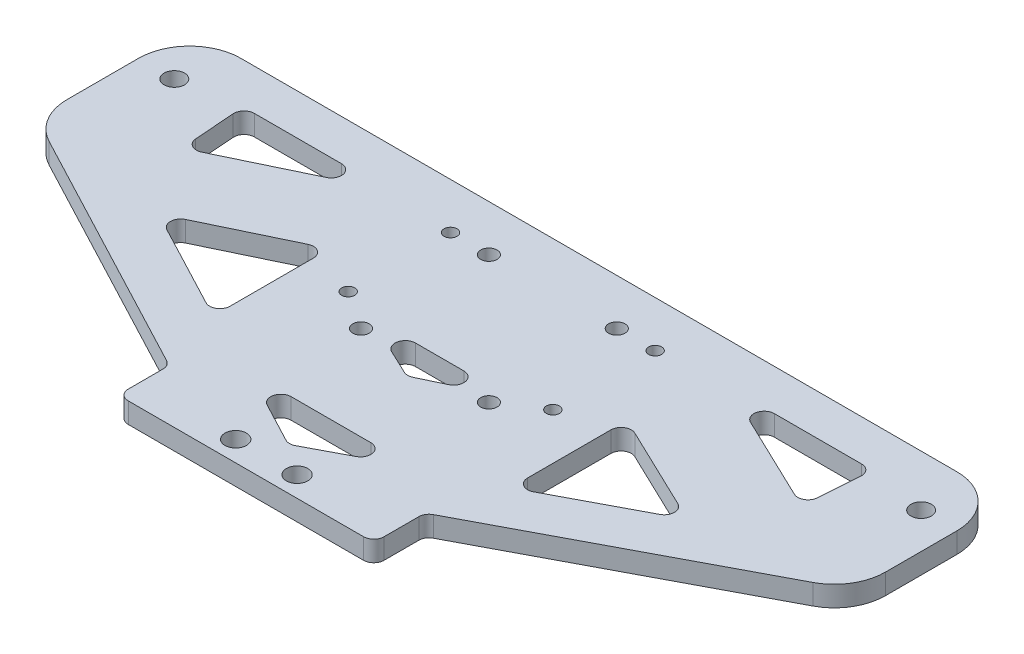
SolidWorks part; units mm, degrees
material "Thornel Mat VMA"
ref_plane "Front" through (0, 0, 0) normal (0, 0, 1) x (1, 0, 0)
ref_plane "Top" through (0, 0, 0) normal (0, 1, 0) x (1, 0, 0)
ref_plane "Right" through (0, 0, 0) normal (1, 0, 0) x (0, 0, -1)
sketch "草图1" plane through (0, 0, 0) normal (0, 1, 0) x (1, 0, 0)
  line L0 (0, 40.0348) -> (0, 0) construction
  line L1 (25, 0) -> (-25, 0)
  line L2 (-25, 0) -> (-80, 29)
  line L3 (-80, 29) -> (-80, 59)
  line L4 (-80, 59) -> (80, 59)
  line L5 (80, 29) -> (80, 59)
  line L6 (25, 0) -> (80, 29)
  point P9 (0, 59)
  dimension "D1" = 59
  dimension "D2" = 80
  dimension "D3" = 25
  dimension "D4" = 30
extrude "凸台-拉伸1" add sketch "草图1" along normal blind 4
sketch "草图2" plane through (0, 4, 0) normal (0, 1, 0) x (1, 0, 0)
  line L0 (0, 0) -> (0, 59) construction
  line L1 (80, 59) -> (-80, 59) construction
  line L2 (-12.5, 50) -> (-12.5, 25) construction
  line L3 (-12.5, 37.5) -> (12.5, 37.5) construction
  line L4 (12.5, 50) -> (12.5, 25) construction
  circle A0 centre (-12.5, 50) radius 1.6
  circle A3 centre (12.5, 50) radius 1.6
  circle A4 centre (-12.5, 25) radius 1.6
  circle A5 centre (12.5, 25) radius 1.6
  point P14 (0, 37.5)
  dimension "D1" = 3.2
  dimension "D2" = 25
  dimension "D4" = 9
  dimension "D3" = 12.5
extrude "切除-拉伸1" cut sketch "草图2" against normal through all
sketch "草图3" plane through (0, 4, 0) normal (0, 1, 0) x (1, 0, 0)
  line L0 (-80, 59) -> (-80, 29) construction
  line L1 (80, 59) -> (-80, 59) construction
  line L23 (-25, 0) -> (25, 0) construction
  line L24 (-66, 51.4654) -> (-66, 27.9182)
  line L25 (-65.4092, 27.0057) -> (-27.5283, 10.0199)
  line L26 (-26.3885, 11.6151) -> (-64.2694, 52.1482)
  line L27 (-56.7306, 52.8689) -> (-35.4528, 30.1014)
  line L28 (-33.7222, 30.7842) -> (-33.7222, 50.1473)
  line L29 (-34.5642, 51.1347) -> (-55.842, 54.5392)
  line L32 (-25.0141, 55.3637) -> (-28.5345, 50.4614)
  line L33 (-80, 29) -> (-25, 0) construction
  line L34 (-13.5, 37) -> (-13.5, 17) construction
  line L35 (-28.7222, 49.8781) -> (-28.7222, 26.6175)
  line L36 (-26.7299, 26.4935) -> (-23.2096, 54.6564)
  line L37 (-13.5, 37) -> (-12.5, 50) construction
  line L38 (-4.3247, 58.5552) -> (-22.7222, 58.5552) construction
  line L39 (0, 30) -> (0, 0) construction
  line L40 (4.3247, 58.5552) -> (22.7222, 58.5552) construction
  line L41 (7.5, 20.5) -> (7.5, 10.5) construction
  line L42 (26.7299, 26.4935) -> (23.2096, 54.6564)
  line L43 (28.7222, 49.8781) -> (28.7222, 26.6175)
  line L44 (25.0141, 55.3637) -> (28.5345, 50.4614)
  line L45 (34.5642, 51.1347) -> (55.842, 54.5392)
  line L46 (33.7222, 30.7842) -> (33.7222, 50.1473)
  line L47 (56.7306, 52.8689) -> (35.4528, 30.1014)
  line L48 (26.3885, 11.6151) -> (64.2694, 52.1482)
  line L49 (65.4092, 27.0057) -> (27.5283, 10.0199)
  line L50 (66, 51.4654) -> (66, 27.9182)
  line L51 (-12.5, 25) -> (-13.5, 17) construction
  circle A0 centre (-73, 51) radius 2.6
  arc A1 (-23.2096, 54.6564) -> (-25.0141, 55.3637) centre (-24.2018, 54.7804) ccw
  arc A2 (-28.7222, 26.6175) -> (-26.7299, 26.4935) centre (-27.7222, 26.6175) ccw
  arc A3 (-28.7222, 49.8781) -> (-28.5345, 50.4614) centre (-27.7222, 49.8781) cw
  arc A4 (-33.7222, 50.1473) -> (-34.5642, 51.1347) centre (-34.7222, 50.1473) ccw
  arc A5 (-56.7306, 52.8689) -> (-55.842, 54.5392) centre (-56, 53.5517) cw
  arc A6 (-35.4528, 30.1014) -> (-33.7222, 30.7842) centre (-34.7222, 30.7842) ccw
  arc A7 (-26.3885, 11.6151) -> (-27.5283, 10.0199) centre (-27.1191, 10.9323) cw
  arc A8 (-66, 27.9182) -> (-65.4092, 27.0057) centre (-65, 27.9182) ccw
  arc A9 (-66, 51.4654) -> (-64.2694, 52.1482) centre (-65, 51.4654) cw
  arc A10 (66, 51.4654) -> (64.2694, 52.1482) centre (65, 51.4654) ccw
  arc A11 (66, 27.9182) -> (65.4092, 27.0057) centre (65, 27.9182) cw
  arc A12 (26.3885, 11.6151) -> (27.5283, 10.0199) centre (27.1191, 10.9323) ccw
  arc A13 (35.4528, 30.1014) -> (33.7222, 30.7842) centre (34.7222, 30.7842) cw
  arc A14 (56.7306, 52.8689) -> (55.842, 54.5392) centre (56, 53.5517) ccw
  arc A15 (33.7222, 50.1473) -> (34.5642, 51.1347) centre (34.7222, 50.1473) cw
  arc A16 (28.7222, 49.8781) -> (28.5345, 50.4614) centre (27.7222, 49.8781) ccw
  arc A17 (28.7222, 26.6175) -> (26.7299, 26.4935) centre (27.7222, 26.6175) cw
  arc A18 (23.2096, 54.6564) -> (25.0141, 55.3637) centre (24.2018, 54.7804) cw
  circle A19 centre (73, 51) radius 2.6
  circle A20 centre (-13.5, 17) radius 1.6
  circle A21 centre (-13.5, 37) radius 1.6
  circle A22 centre (13.5, 17) radius 1.6
  circle A23 centre (13.5, 37) radius 1.6
  point P24 (-28.7222, 10.5552)
  point P32 (-28.7222, 50.2)
  point P35 (-33.7222, 51)
  point P38 (-58.7222, 55)
  point P43 (-23, 7.9894)
  point P46 (-66, 27.2707)
  point P49 (-66, 54)
  point P86 (66, 54)
  point P87 (66, 27.2707)
  point P88 (23, 7.9894)
  point P89 (58.7222, 55)
  point P90 (33.7222, 51)
  point P91 (28.7222, 50.2)
  point P92 (28.7222, 10.5552)
  dimension "D1" = 5.2
  dimension "D2" = 7
  dimension "D3" = 8
  dimension "D15" = 1
  dimension "D16" = 3.2
  dimension "D17" = 27
  dimension "D18" = 17
  dimension "D20" = 3.2
  dimension "D4" = 7
  dimension "D5" = 5
  dimension "D6" = 5
  dimension "D7" = 8
  dimension "D8" = 6
  dimension "D9" = 4
  dimension "D10" = 8
  dimension "D11" = 2
  dimension "D12" = 5
  dimension "D13" = 25
  dimension "D14" = 6
  dimension "D19" = 20
extrude "切除-拉伸2" [suppressed] cut sketch "草图3" against normal through all
fillet "圆角1" [suppressed] radius 7
sketch "草图4" plane through (0, 4, 0) normal (0, 1, 0) x (1, 0, 0)
  line L0 (0, 0) -> (0, 67.0073) construction
  line L1 (80, 59) -> (-80, 59) construction
  circle A0 centre (20, 50) radius 1.275
  circle A2 centre (20, 30) radius 1.275
  circle A3 centre (-20, 30) radius 1.275
  circle A4 centre (-20, 50) radius 1.275
  dimension "D1" = 2.55
  dimension "D2" = 20
  dimension "D4" = 9
  dimension "D5" = 20
  dimension "D3" = 2
extrude "切除-拉伸3" cut sketch "草图4" against normal blind 10
sketch "草图6" plane through (0, 4, 0) normal (0, 1, 0) x (1, 0, 0)
  line L1 (-25, 0) -> (25, 0)
  line L2 (-25, 0) -> (-25, -10)
  line L3 (-25, -10) -> (25, -10)
  line L4 (25, 0) -> (25, -10)
  dimension "D1" = 50
  dimension "D2" = 10
extrude "凸台-拉伸2" add sketch "草图6" against normal up to surface (4 mm away) up to face at (-20, 0, -51.275)
sketch "草图7" plane through (0, 4, 0) normal (0, 1, 0) x (1, 0, 0)
  line L0 (0, 0) -> (0, -33.3189) construction
  line L1 (-25, -10) -> (25, -10) construction
  circle A0 centre (-6, -6) radius 2.1
  circle A1 centre (6, -6) radius 2.1
  dimension "D1" = 4.2
  dimension "D2" = 6
  dimension "D3" = 4
extrude "切除-拉伸4" cut sketch "草图7" against normal blind 10
sketch "草图8" plane through (0, 4, 0) normal (0, 1, 0) x (1, 0, 0)
  line L0 (-80, 59) -> (-80, 29) construction
  line L1 (80, 59) -> (-80, 59) construction
  line L2 (0, 0) -> (0, 67.9824) construction
  circle A0 centre (-73, 49) radius 2
  circle A1 centre (73, 49) radius 2
  dimension "D1" = 4
  dimension "D2" = 7
  dimension "D3" = 10
extrude "切除-拉伸5" cut sketch "草图8" against normal blind 10
sketch "草图9" plane through (0, 4, 0) normal (0, 1, 0) x (1, 0, 0)
  line L0 (0, 0) -> (0, 79.7791) construction
  line L1 (-13.6072, 27.8756) -> (13.6072, 27.8756)
  line L2 (-13.6072, 27.8756) -> (0, 21.4248)
  line L3 (-61.5112, 51) -> (-33.5112, 51)
  line L4 (-33.5112, 51) -> (-60.5648, 38.0345)
  line L5 (-60.5648, 38.0345) -> (-61.5112, 51)
  line L6 (-51.7088, 24.599) -> (-29.0798, 35.444)
  line L7 (-29.0798, 35.444) -> (-29.0798, 12.6673)
  line L8 (-29.0798, 12.6673) -> (-51.7088, 24.599)
  line L9 (29.0798, 12.6673) -> (51.7088, 24.599)
  line L10 (29.0798, 35.444) -> (29.0798, 12.6673)
  line L11 (51.7088, 24.599) -> (29.0798, 35.444)
  line L12 (60.5648, 38.0345) -> (61.5112, 51)
  line L13 (33.5112, 51) -> (60.5648, 38.0345)
  line L14 (61.5112, 51) -> (33.5112, 51)
  line L15 (13.6072, 27.8756) -> (0, 21.4248)
  line L16 (80, 59) -> (-80, 59) construction
  line L17 (-80, 29) -> (-25, 0) construction
  line L18 (-80, 59) -> (-80, 29) construction
  point P19 (0, 27.8756)
  dimension "D1" = 28
  dimension "D2" = 8
  dimension "D3" = 13
  dimension "D4" = 30
extrude "切除-拉伸6" cut sketch "草图9" against normal blind 10
sketch "草图10" plane through (0, 4, 0) normal (0, 1, 0) x (1, 0, 0)
  line L0 (0, 0) -> (0, -26.7425) construction
  line L1 (0, 0) -> (0, 25.9451) construction
  line L2 (-15.8628, 6.6366) -> (15.8628, 6.6366)
  line L3 (15.8628, 6.6366) -> (0, -1.7274)
  line L4 (25, 0) -> (80, 29) construction
  line L5 (-15.8628, 6.6366) -> (0, -1.7274)
  point P11 (0, 6.6366)
extrude "切除-拉伸7" cut sketch "草图10" against normal blind 10
fillet "圆角2" radius 2 22 edges at (-25, 2, 0) (-25, 2, 10) (25, 2, 10) (25, 2, 0) (-13.6072, 2, -27.8756) (13.6072, 2, -27.8756) (0, 2, -21.4248) (-51.7088, 2, -24.599) (-29.0798, 2, -35.444) (-29.0798, 2, -12.6673) (-61.5112, 2, -51) (-33.5112, 2, -51) (-60.5648, 2, -38.0345) (33.5112, 2, -51) (61.5112, 2, -51) (60.5648, 2, -38.0345) (29.0798, 2, -35.444) (51.7088, 2, -24.599) (0, 2, 1.7274) (-15.8628, 2, -6.6366) (15.8628, 2, -6.6366) (29.0798, 2, -12.6673)
fillet "圆角3" radius 10 4 edges at (-80, 2, -29) (80, 2, -59) (80, 2, -29) (-80, 2, -59)
